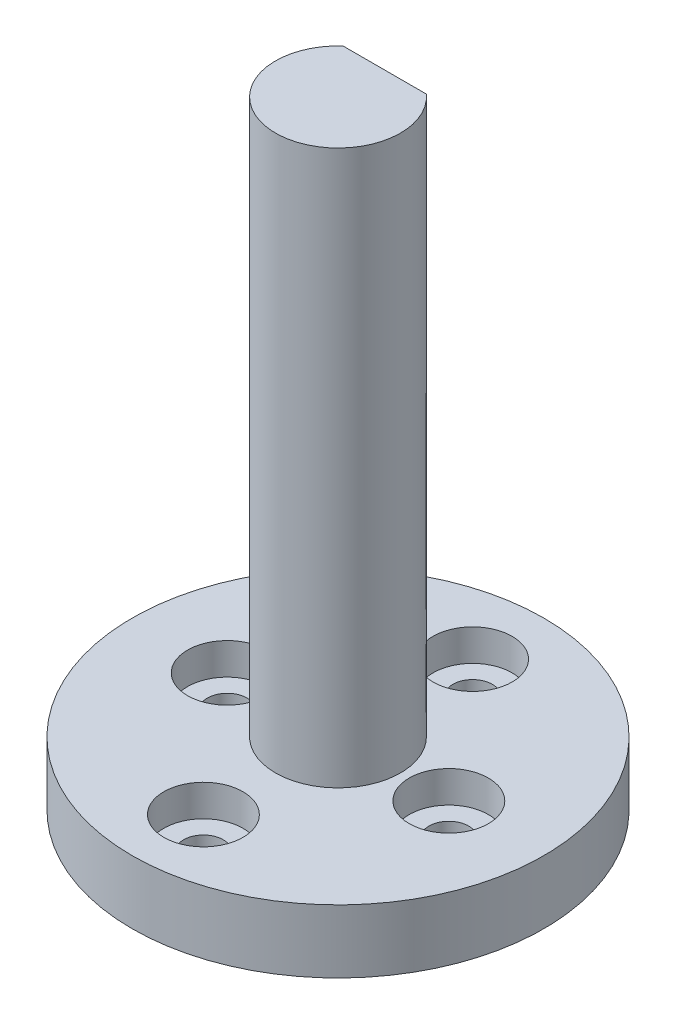
SolidWorks part; units mm, degrees
ref_plane "Alzado" through (0, 0, 0) normal (0, 0, 1) x (1, 0, 0)
ref_plane "Planta" through (0, 0, 0) normal (0, 1, 0) x (1, 0, 0)
ref_plane "Vista lateral" through (0, 0, 0) normal (1, 0, 0) x (0, 0, -1)
sketch "Croquis3" plane through (0, 0, 0) normal (0, 1, 0) x (1, 0, 0)
  circle A0 centre (0, 0) radius 13
  dimension "D1" = 26
extrude "Saliente-Extruir1" add sketch "Croquis3" along normal blind 4
sketch "Croquis4" plane through (0, 4, 0) normal (0, 1, 0) x (1, 0, 0)
  circle A0 centre (0, 0) radius 3.95
  dimension "D1" = 7.9
extrude "Saliente-Extruir2" add sketch "Croquis4" along normal blind 35
sketch "Croquis5" plane through (0, 39, 0) normal (0, 1, 0) x (1, 0, 0)
  line L0 (0, 3.95) -> (0, 2.95) construction
  line L1 (2.6268, 2.95) -> (-2.6268, 2.95)
  circle A0 centre (0, 0) radius 3.95 construction
  arc A1 (2.6268, 2.95) -> (-2.6268, 2.95) centre (0, 0) ccw
  dimension "D1" = 1
extrude "Cortar-Extruir1" cut sketch "Croquis5" against normal blind 20
sketch "Croquis7" plane through (0, 0, 0) normal (0, -1, 0) x (1, 0, 0)
  circle A0 centre (0, 0) radius 12
  dimension "D1" = 24
sketch "Croquis8" plane through (0, 0, 0) normal (0, -1, 0) x (1, 0, 0)
  line L0 (0, -10.2812) -> (0, 10.4112) construction
  line L1 (-11.52, 0) -> (11.5297, 0) construction
  circle A1 centre (0, 8.5) radius 1.25
  circle A2 centre (0, -8.5) radius 1.25
  circle A3 centre (-7, 0) radius 1.25
  circle A4 centre (7, 0) radius 1.25
  dimension "D1" = 8.5
  dimension "D2" = 2.5
  dimension "D3" = 7
extrude "Cortar-Extruir3" cut sketch "Croquis8" against normal through all both and the other way through all
sketch "Croquis10" plane through (0, 4, 0) normal (0, 1, 0) x (1, 0, 0)
  circle A0 centre (0, -8.5) radius 1.25 construction
  circle A1 centre (0, 8.5) radius 1.25 construction
  circle A2 centre (0, -8.5) radius 1.25 construction
  circle A3 centre (0, 8.5) radius 1.25 construction
  circle A4 centre (0, 8.5) radius 2.5
  circle A5 centre (0, -8.5) radius 2.5
  circle A6 centre (7, 0) radius 1.25 construction
  circle A7 centre (-7, 0) radius 1.25 construction
  circle A8 centre (7, 0) radius 1.25
  circle A9 centre (-7, 0) radius 1.25
  circle A10 centre (-7, 0) radius 2.5
  circle A11 centre (7, 0) radius 2.5
  dimension "D1" = 5
  dimension "D2" = 5
extrude "Cortar-Extruir5" cut sketch "Croquis10" against normal blind 2 and the other way through all
sketch "Croquis9" plane through (0, 0, 0) normal (0, 1, 0) x (1, 0, 0)
  circle A0 centre (0, 0) radius 1.625
  dimension "D1" = 3.25
extrude "Cortar-Extruir4" cut sketch "Croquis9" along normal blind 3
sketch "Croquis11" plane through (0, 0, 0) normal (0, -1, 0) x (1, 0, 0)
  circle A0 centre (0, 0) radius 4
  dimension "D1" = 8
extrude "Cortar-Extruir6" cut sketch "Croquis11" against normal blind 0.5
